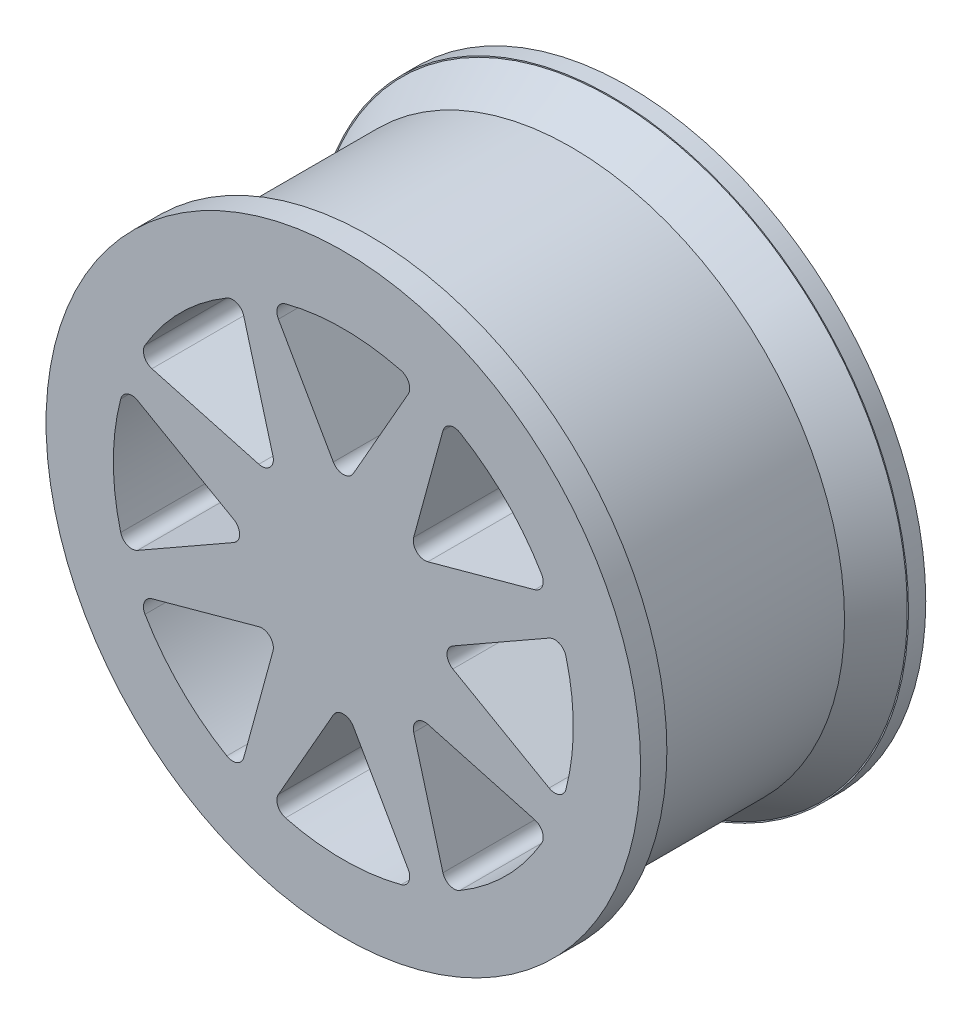
SolidWorks part; units mm, degrees
ref_plane "Alzado" through (0, 0, 0) normal (0, 0, 1) x (1, 0, 0)
ref_plane "Planta" through (0, 0, 0) normal (0, 1, 0) x (1, 0, 0)
ref_plane "Vista lateral" through (0, 0, 0) normal (1, 0, 0) x (0, 0, -1)
sketch "Croquis2" plane through (0, 0, 0) normal (1, 0, 0) x (0, 0, -1)
  line L0 (0, 0) -> (0, 29.9479) construction
  line L1 (-4.764, 0) -> (19.1886, 0) construction
  line L2 (-10.9, 23.75) -> (10.9, 23.75)
  line L3 (10.9, 23.75) -> (10.9, 25.85)
  line L4 (10.9, 25.85) -> (12.4, 25.85)
  line L5 (12.4, 25.85) -> (12.4, 0)
  line L6 (-12.4, 25.85) -> (-12.4, 0)
  line L7 (-10.9, 25.85) -> (-12.4, 25.85)
  line L8 (-10.9, 23.75) -> (-10.9, 25.85)
  line L9 (-12.4, 0) -> (12.4, 0)
  point P15 (0, 23.75)
  dimension "D1" = 47.5
  dimension "D2" = 21.8
  dimension "D3" = 51.7
  dimension "D4" = 1.5
revolve "Revolución2" add sketch "Croquis2" angle 360 about L9
sketch "Croquis3" plane through (0, 0, 12.4) normal (0, 0, 1) x (1, 0, 0)
  circle A0 centre (0, 0) radius 22.5
  dimension "D1" = 45
extrude "Cortar-Extruir1" cut sketch "Croquis3" against normal up to next
sketch "Croquis4" plane through (0, 0, 12.4) normal (0, 0, 1) x (1, 0, 0)
  line L0 (0, 22.5) -> (0, -22.5) construction
  line L1 (-22.5, 0) -> (22.5, 0) construction
  line L2 (-6.2704, 18.9916) -> (0, 8)
  line L3 (0, 8) -> (6.2704, 18.9916)
  line L4 (5.6569, 5.6569) -> (17.863, 8.9953)
  line L5 (8.9953, 17.863) -> (5.6569, 5.6569)
  line L6 (8, 0) -> (18.9916, -6.2704)
  line L7 (18.9916, 6.2704) -> (8, 0)
  line L8 (5.6569, -5.6569) -> (8.9953, -17.863)
  line L9 (17.863, -8.9953) -> (5.6569, -5.6569)
  line L10 (0, -8) -> (-6.2704, -18.9916)
  line L11 (6.2704, -18.9916) -> (0, -8)
  line L12 (-5.6569, -5.6569) -> (-17.863, -8.9953)
  line L13 (-8.9953, -17.863) -> (-5.6569, -5.6569)
  line L14 (-8, 0) -> (-18.9916, 6.2704)
  line L15 (-18.9916, -6.2704) -> (-8, 0)
  line L16 (-5.6569, 5.6569) -> (-8.9953, 17.863)
  line L17 (-17.863, 8.9953) -> (-5.6569, 5.6569)
  circle A0 centre (0, 0) radius 22.5
  circle A1 centre (0, 0) radius 22.5 construction
  circle A2 centre (0, 0) radius 20
  point P37 (0, 0)
  circle M3 centre (0, 0) radius 22.5
  dimension "D1" = 40
  dimension "D2" = 8
  dimension "D3" = 12.5408
  dimension "D4" = 8
extrude "Saliente-Extruir1" add sketch "Croquis4" against normal blind 10 contours A2 M3 | L7 A2 L4 L5 L3 L2 L16 L17 L14 L15 L12 L13 L10 L11 L8 L9 L6
fillet "Redondeo2" radius 1 24 edges at (18.9916, -6.2704, 7.4) (8, 0, 7.4) (18.9916, 6.2704, 7.4) (8.9953, -17.863, 7.4) (5.6569, -5.6569, 7.4) (17.863, -8.9953, 7.4) (-6.2704, -18.9916, 7.4) (0, -8, 7.4) (6.2704, -18.9916, 7.4) (-17.863, -8.9953, 7.4) (-5.6569, -5.6569, 7.4) (-8.9953, -17.863, 7.4) (-8.9953, 17.863, 7.4) (-5.6569, 5.6569, 7.4) (-17.863, 8.9953, 7.4) (6.2704, 18.9916, 7.4) (0, 8, 7.4) (-6.2704, 18.9916, 7.4) (17.863, 8.9953, 7.4) (5.6569, 5.6569, 7.4) (8.9953, 17.863, 7.4) (-8, 0, 7.4) (-18.9916, 6.2704, 7.4) (-18.9916, -6.2704, 7.4)
sketch "Croquis6" plane through (0, 0, 2.4) normal (0, 0, -1) x (-1, 0, 0)
  circle A0 centre (0, 0) radius 6
  dimension "D1" = 12
extrude "Saliente-Extruir2" add sketch "Croquis6" along normal blind 17.8
sketch "Croquis7" plane through (0, 0, -15.4) normal (0, 0, -1) x (-1, 0, 0)
  line L0 (1.35, 1.5427) -> (1.35, -1.5427)
  circle A0 centre (0, 0) radius 2.05
  point P5 (-2.05, 0)
  dimension "D1" = 4.1
  dimension "D2" = 3.4
extrude "Cortar-Extruir3" cut sketch "Croquis7" against normal blind 9.5 contours L0 A0
sketch "Croquis8" plane through (0, 0, -15.4) normal (0, 0, -1) x (-1, 0, 0)
  line L0 (-2.1664, -0.5421) -> (-3.8626, 0) construction
  line L1 (-1.8371, -0.9098) -> (-3.9387, -0.2381)
  line L2 (-2.0241, -0.3251) -> (-3.7865, 0.2381)
  line L3 (-1.9575, -0.6088) -> (-2.4645, 1.0211) construction
  line L4 (-2.05, 0) -> (-3.8626, 0) construction
  line L5 (0, 0) -> (-2.05, 0) construction
  line L6 (-2.0903, -0.304) -> (-2.0241, -0.3251) construction
  line L7 (-2.2425, -0.7802) -> (-1.8371, -0.9098) construction
  arc A0 (1.35, 1.5427) -> (1.35, -1.5427) centre (0, 0) ccw construction
  arc A1 (1.35, 1.5427) -> (-2.0241, -0.3251) centre (0, 0) ccw construction
  arc A2 (-2.2425, -0.7802) -> (-2.0903, -0.304) centre (-2.1664, -0.5421) ccw construction
  arc A3 (-3.7865, 0.2381) -> (-3.9387, -0.2381) centre (-3.8626, 0) ccw
  arc A4 (-1.9575, -0.6088) -> (-1.8371, -0.9098) centre (0, 0) ccw
  arc A5 (-1.8371, -0.9098) -> (1.35, -1.5427) centre (0, 0) ccw construction
  arc A6 (-2.0241, -0.3251) -> (-1.9575, -0.6088) centre (0, 0) ccw
  point P5 (-2.05, 0)
  dimension "D1" = 55
  dimension "D2" = 2
  dimension "D3" = 0.5
extrude "Cortar-Extruir4" cut sketch "Croquis8" against normal up to surface (9.5 mm away) up to face at (0.35, 0, -5.9)
pattern_circular "MatrizC1" count 4 over 120 about axis through (0, 0, 0) along (0, 0, 1) of "Cortar-Extruir4"
fillet "Redondeo3" radius 3 1 edges at (6, 0, 2.4)
sketch "Croquis9" plane through (0, 0, -15.4) normal (0, 0, -1) x (-1, 0, 0)
  line L0 (1.35, 1.5427) -> (1.35, -1.5427) construction
  line L1 (1.35, 1.5427) -> (1.35, -1.5427)
  line L2 (1.35, -1.5427) -> (1.35, -5.8462)
  line L3 (1.35, 1.5427) -> (1.35, 5.8462)
  circle A0 centre (0, 0) radius 6 construction
  arc A1 (1.35, -5.8462) -> (1.35, 5.8462) centre (0, 0) ccw
  arc A2 (1.35, 5.8462) -> (1.35, -5.8462) centre (0, 0) ccw construction
extrude "Saliente-Extruir3" add sketch "Croquis9" against normal blind 7
chamfer "Chaflán1" distance 2 angle 60 2 edges at (23.75, 0, -10.9) (23.75, 0, 10.9)
